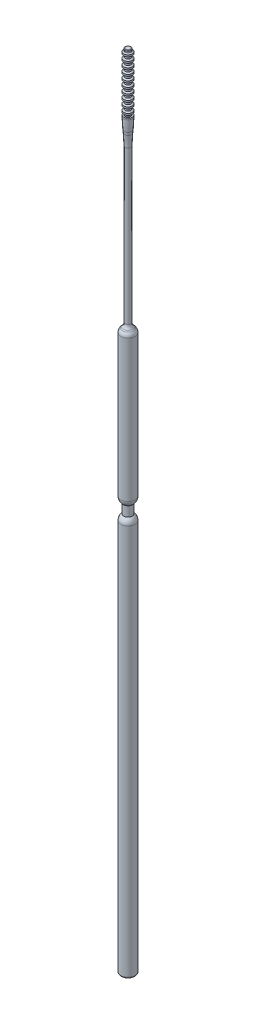
SolidWorks part; units mm, degrees
ref_plane "Front Plane" through (0, 0, 0) normal (0, 0, 1) x (1, 0, 0)
ref_plane "Top Plane" through (0, 0, 0) normal (0, 1, 0) x (1, 0, 0)
ref_plane "Right Plane" through (0, 0, 0) normal (1, 0, 0) x (0, 0, -1)
sketch "Sketch2" plane through (0, 0, 0) normal (0, 1, 0) x (1, 0, 0)
  circle A0 centre (0, 0) radius 0.5
  dimension "D1" = 1
extrude "Boss-Extrude1" add sketch "Sketch2" along normal blind 5
sketch "Sketch4" plane through (0, 0, 0) normal (1, 0, 0) x (0, 0, -1)
  line L0 (0, 5) -> (0, 10.5)
  line L1 (0.5, 5) -> (-0.5, 5) construction
  line L2 (0, 10.5) -> (0.75, 10.5)
  line L3 (0.75, 10.5) -> (0.75, 9)
  line L4 (0.5, 5) -> (0.5, 6.5)
  line L5 (0.5, 6.5) -> (0.75, 9)
  line L6 (0, 5) -> (0.5, 5)
  point P5 (0.75, 9)
  point P7 (0.5, 6.5)
  dimension "D1" = 5.5
  dimension "D2" = 0.75
  dimension "D3" = 1.5
  dimension "D4" = 1.5
  dimension "D5" = 0.5
revolve "Revolve1" add sketch "Sketch4" angle 360 about L0
fillet "Fillet1" radius 20 2 edges at (0, 9, -0.75) (0, 6.5, -0.5)
sketch "Sketch5" plane through (0, 10.5, 0) normal (0, 1, 0) x (1, 0, 0)
  line L2 (-0.125, 0.7395) -> (-0.125, -0.7395)
  line L4 (0.125, 0.7395) -> (0.125, -0.7395)
  line L5 (-0.7395, 0.125) -> (0.7395, 0.125)
  line L7 (-0.7395, -0.125) -> (0.7395, -0.125)
  circle A0 centre (0, 0) radius 0.75
  circle A1 centre (0, 0) radius 0.5
  circle A2 centre (0, 0) radius 0.5
  dimension "D1" = 1
  dimension "D6" = 1.5
  dimension "0.5" = 1
  dimension "D2" = 0.125
  dimension "D3" = 0.25
  dimension "D4" = 0.125
  dimension "D5" = 0.25
extrude "Boss-Extrude3" add sketch "Sketch5" along normal blind 1 contours L4 A2 L2 L5 | L7 A2 L5 L4 | L5 A2 L4 | L4 A2 L7 | L2 A2 L4 L7 | L2 L7 L4 L5 | L5 A2 L7 L2 | L2 A2 L5 | L7 A2 L2
sketch "Sketch10" plane through (0, 0, 0) normal (0, 0, 1) x (1, 0, 0)
  line L0 (0, 11.5) -> (0.75, 10.9748)
  line L1 (0.5, 11.5) -> (-0.5, 11.5) construction
  line L2 (0.75, 10.6697) -> (0.75, 10.9748)
  line L3 (0, 11.1948) -> (0.75, 10.6697)
  line L4 (0, 11.5) -> (0, 11.1948)
  dimension "D1" = 35
  dimension "D2" = 0.25
revolve "Revolve5" add sketch "Sketch10" angle 360 about L4
other "Move Face1" face at (0, 10.5, 0.5) parameters "D1"=0.25
sketch "Sketch8" plane through (0, 0, 0) normal (0, -1, 0) x (-1, 0, 0)
  circle A0 centre (0, 0) radius 0.5
extrude "Boss-Extrude4" add sketch "Sketch8" along normal blind 21.5
sketch "Sketch9" plane through (0, 0, 0) normal (0, 0, 1) x (1, 0, 0)
  line L0 (-0.5, -21.5) -> (-0.5, -22)
  line L1 (-0.5, -22) -> (-1.25, -22.75)
  line L2 (-1.25, -22.75) -> (-1.25, -23.25)
  line L3 (-0.5, 5.5025) -> (-0.5, -21.5) construction
  line L4 (-1.25, -23.25) -> (-1.25, -48.25)
  line L5 (-0.5, -21.5) -> (0, -21.5)
  line L6 (0, -48.25) -> (0, -52)
  line L8 (-1.25, -52) -> (-1.25, -120.25)
  line L9 (-1.25, -120.25) -> (-1.25, -121.5)
  line L10 (0, -21.5) -> (0, -121.5)
  line L11 (-0.5, -21.5) -> (0.5, -21.5) construction
  line L12 (0, -121.5) -> (-1.25, -121.5)
  line L13 (-0.75, -49.25) -> (-0.75, -51)
  arc A1 (-0.75, -51) -> (-1.25, -52) centre (0, -52) ccw
  arc A2 (-1.25, -48.25) -> (-0.75, -49.25) centre (0, -48.25) ccw
  dimension "D7" = 3.75
  dimension "D10" = 0.75
  dimension "D1" = 0.75
  dimension "D2" = 0.5
  dimension "D3" = 0.5
  dimension "D4" = 0.75
  dimension "D5" = 25
  dimension "D6" = 1.25
  dimension "D8" = 68.25
  dimension "D9" = 1.25
  dimension "D11" = 0.75
revolve "Revolve4" add sketch "Sketch9" angle 360 about L10
fillet "Fillet6" radius 0.25 1 edges at (0, -121.5, 1.25)
fillet "Fillet7" radius 1 2 edges at (0, -22.75, 1.25) (0, -22, 0.5)
pattern_linear "LPattern1" count 10 spacing 1 along (0, 1, 0) of "Revolve5", "Boss-Extrude3"
fillet "Fillet8" radius 0.1 2 edges at (0.5, 20.1499, 0) (0, 20.5, 0.5)
